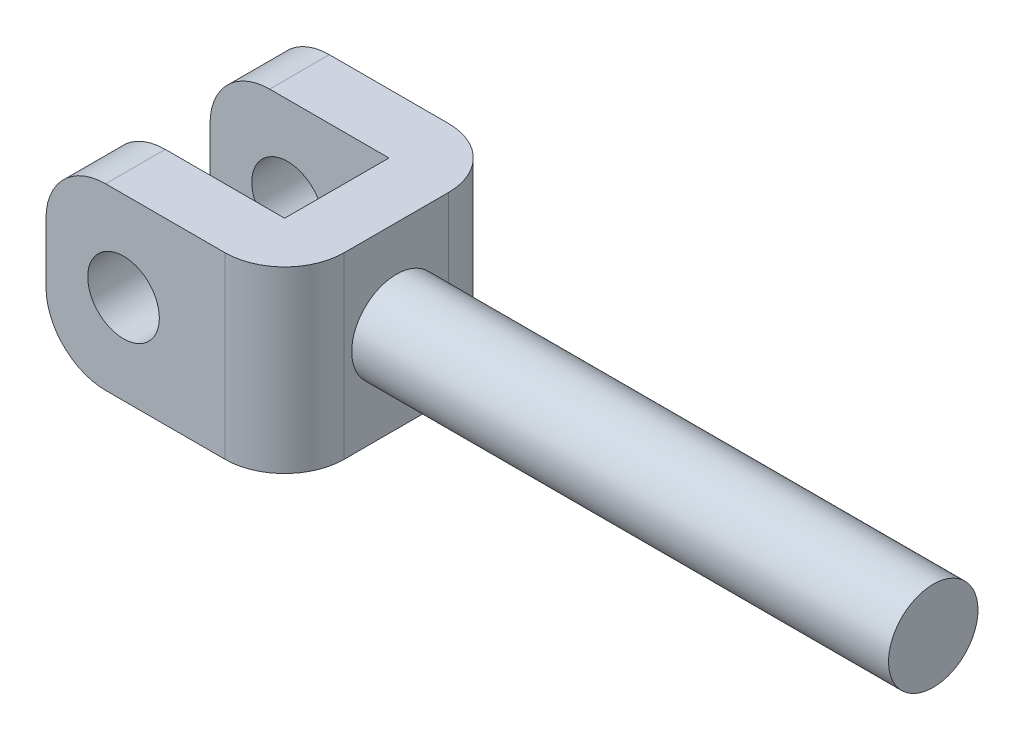
SolidWorks part; units mm, degrees
ref_plane "Front Plane" through (0, 0, 0) normal (0, 0, 1) x (1, 0, 0)
ref_plane "Top Plane" through (0, 0, 0) normal (0, 1, 0) x (1, 0, 0)
ref_plane "Right Plane" through (0, 0, 0) normal (1, 0, 0) x (0, 0, -1)
sketch "Sketch1" plane through (0, 0, 0) normal (1, 0, 0) x (0, 0, -1)
  circle A0 centre (0, 0) radius 0.75
  dimension "D1" = 1.5
extrude "Boss-Extrude1" add sketch "Sketch1" along normal blind 10
sketch "Sketch2" plane through (0, 0, 0) normal (0, 1, 0) x (1, 0, 0)
  line L0 (1, 1.875) -> (1, -1.875)
  line L2 (0, 0.875) -> (0, -0.875)
  line L5 (1, -1.875) -> (-3, -1.875)
  line L6 (-3, 1.875) -> (-3, 0.875)
  line L7 (1, 1.875) -> (-3, 1.875)
  line L8 (0, 0.875) -> (-3, 0.875)
  line L10 (-3, -0.875) -> (0, -0.875)
  line L11 (-3, -0.875) -> (-3, -1.875)
  point P1 (0, 0)
  dimension "D1" = 4
  dimension "D2" = 0
extrude "Boss-Extrude2" add sketch "Sketch2" along normal blind 1.5 and the other way blind 1.5
fillet "Fillet1" radius 1 6 edges at (-3, 1.5, -1.375) (-3, -1.5, -1.375) (-3, -1.5, 1.375) (-3, 1.5, 1.375) (1, 0, -1.875) (1, 0, 1.875)
sketch "Sketch3" plane through (0, 0, -1.875) normal (0, 0, -1) x (-1, 0, 0)
  line L0 (0, -1.5) -> (2, -1.5) construction
  line L2 (0, 1.5) -> (0, -1.5) construction
  circle A0 centre (1.7, 0) radius 0.6
  dimension "D1" = 1.2
  dimension "D2" = 1.5
  dimension "D3" = 1.7
extrude "Cut-Extrude1" cut sketch "Sketch3" against normal blind 5
